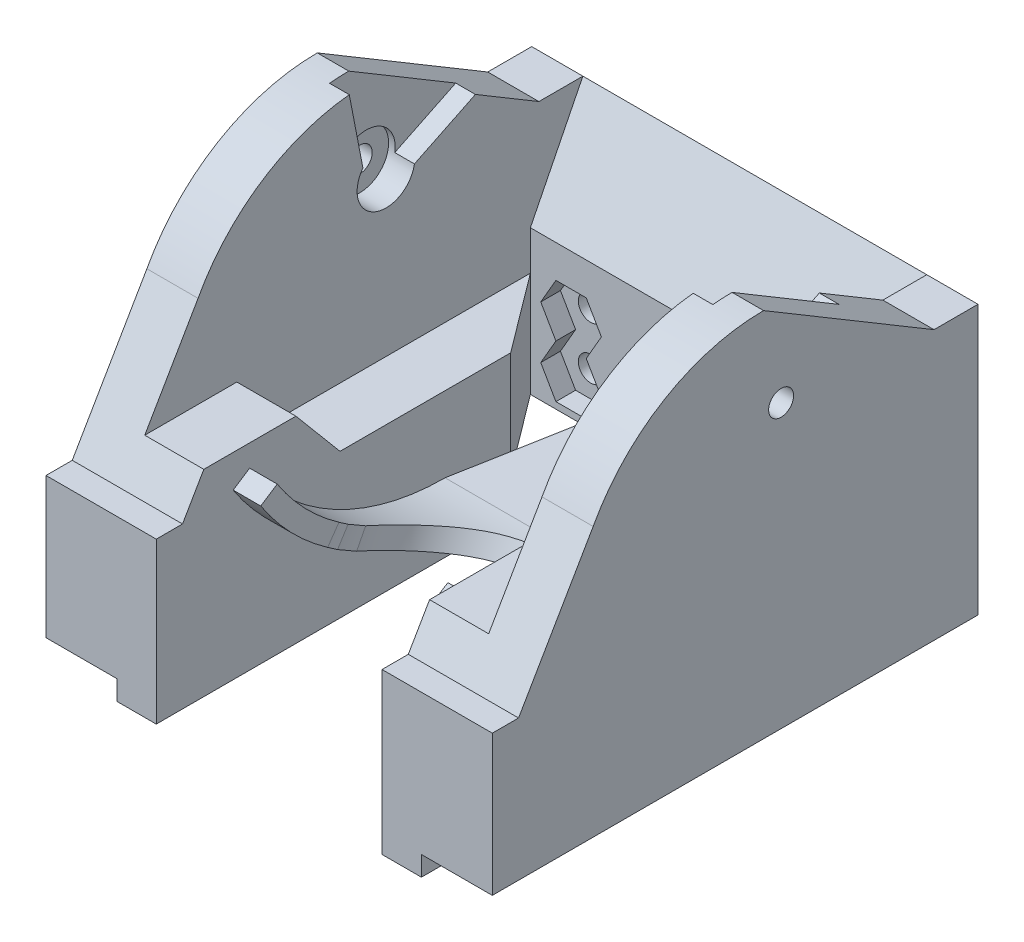
SolidWorks part; units mm, degrees
ref_plane "Alzado" through (0, 0, 0) normal (0, 0, 1) x (1, 0, 0)
ref_plane "Planta" through (0, 0, 0) normal (0, 1, 0) x (1, 0, 0)
ref_plane "Vista lateral" through (0, 0, 0) normal (1, 0, 0) x (0, 0, -1)
sketch "Croquis1" plane through (0, 0, 0) normal (0, 0, 1) x (1, 0, 0)
  line L1 (-48.8873, 14.6225) -> (-14.8873, 14.6225)
  line L2 (-48.8873, 14.6225) -> (-48.8873, -4.3775)
  line L3 (-48.8873, -4.3775) -> (-14.8873, -4.3775)
  line L4 (-14.8873, 14.6225) -> (-14.8873, -4.3775)
  dimension "D1" = 19
  dimension "D2" = 34
extrude "Saliente-Extruir1" add sketch "Croquis1" along normal blind 35
sketch "Croquis2" plane through (0, -4.3775, 0) normal (0, -1, 0) x (1, 0, 0)
  line L0 (-48.8873, 35) -> (-14.8873, 35) construction
  line L1 (-44.9873, 35) -> (-18.7873, 35)
  line L2 (-44.9873, 35) -> (-44.9873, 4)
  line L3 (-44.9873, 4) -> (-18.7873, 4)
  line L4 (-18.7873, 35) -> (-18.7873, 4)
  line L5 (-48.8873, 35) -> (-48.8873, 0) construction
  line L6 (-14.8873, 35) -> (-14.8873, 0) construction
  line L7 (-48.8873, 0) -> (-14.8873, 0) construction
  dimension "D1" = 3.9
  dimension "D2" = 3.9
  dimension "D3" = 26.2
  dimension "D4" = 4
extrude "Cortar-Extruir1" cut sketch "Croquis2" against normal blind 25
sketch "Croquis4" plane through (-18.7873, 0, 0) normal (-1, 0, 0) x (0, 0, 1)
  line L0 (4, 14.6225) -> (4, 6.6225)
  line L1 (4, 14.6225) -> (4, -4.3775) construction
  line L2 (4, 6.6225) -> (0, 14.6225)
  line L3 (0, 14.6225) -> (4, 14.6225)
extrude "Cortar-Extruir3" cut sketch "Croquis4" along normal up to vertex (26.2 mm away) up to point (-44.9873, 14.6225, 4)
sketch "Croquis9" plane through (-14.8873, 0, 0) normal (1, 0, 0) x (0, 0, -1)
  line L0 (-35, 14.6225) -> (0, 14.6225) construction
  line L1 (-29.3158, 14.6225) -> (-3.3495, 14.6225)
  line L7 (-35, -4.3775) -> (0, -4.3775) construction
  arc A0 (-29.3158, 14.6225) -> (-3.3495, 14.6225) centre (-16.3327, 7.6225) cw
  dimension "D2" = 12
extrude "Saliente-Extruir2" add sketch "Croquis9" against normal up to vertex (34 mm away) up to point (-48.8873, 14.6225, 35)
sketch "Croquis10" plane through (0, 14.6225, 0) normal (0, -1, 0) x (1, 0, 0)
  line L1 (-44.9873, 29.3158) -> (-18.7873, 29.3158)
  line L2 (-44.9873, 29.3158) -> (-44.9873, 3.3495)
  line L3 (-44.9873, 3.3495) -> (-18.7873, 3.3495)
  line L4 (-18.7873, 29.3158) -> (-18.7873, 3.3495)
extrude "Cortar-Extruir4" cut sketch "Croquis10" against normal blind 10
sketch "Croquis18" plane through (0, 0, 0) normal (0, 0, -1) x (-1, 0, 0)
  line L0 (48.8873, -4.3775) -> (14.8873, -4.3775) construction
  line L2 (48.8873, 14.6225) -> (48.8873, -4.3775) construction
  circle A0 centre (41.8873, -1.8775) radius 0.95
  circle A1 centre (21.8873, -1.8775) radius 0.95
  circle A2 centre (21.8873, 2.1225) radius 0.95
  circle A3 centre (41.8873, 2.1225) radius 0.95
  dimension "D1" = 2.5
  dimension "D2" = 7
  dimension "D5" = 4
  dimension "D3" = 2
  dimension "D4" = 2
extrude "Cortar-Extruir11" cut sketch "Croquis18" against normal up to vertex (4 mm away) up to point (-18.7873, -4.3775, 4)
sketch "Croquis19" plane through (0, 0, 4) normal (0, 0, 1) x (1, 0, 0)
  line L0 (-44.1973, -1.8775) -> (-43.0423, -3.878)
  line L1 (-24.1973, -1.8775) -> (-23.0423, -3.878)
  line L2 (-23.0423, -3.878) -> (-20.7323, -3.878)
  line L3 (-20.7323, -3.878) -> (-19.5773, -1.8775)
  line L4 (-19.5773, -1.8775) -> (-20.732, 0.1225)
  line L6 (-23.0426, 0.1225) -> (-24.1973, -1.8775)
  line L7 (-43.0423, -3.878) -> (-40.7323, -3.878)
  line L8 (-40.7323, -3.878) -> (-39.5773, -1.8775)
  line L9 (-39.5773, -1.8775) -> (-40.732, 0.1225)
  line L11 (-43.0426, 0.1225) -> (-44.1973, -1.8775)
  line L12 (-44.1973, 2.1225) -> (-43.0426, 0.1225)
  line L14 (-40.732, 0.1225) -> (-39.5773, 2.1225)
  line L15 (-39.5773, 2.1225) -> (-40.7323, 4.1231)
  line L16 (-40.7323, 4.1231) -> (-43.0423, 4.1231)
  line L17 (-43.0423, 4.1231) -> (-44.1973, 2.1225)
  line L18 (-24.1973, 2.1225) -> (-23.0426, 0.1225)
  line L20 (-20.732, 0.1225) -> (-19.5773, 2.1225)
  line L21 (-19.5773, 2.1225) -> (-20.7323, 4.1231)
  line L22 (-20.7323, 4.1231) -> (-23.0423, 4.1231)
  line L23 (-23.0423, 4.1231) -> (-24.1973, 2.1225)
  line L45 (-20.7323, 0.1231) -> (-23.0423, 0.1231) [skipped]
  line L46 (-23.0423, 0.122) -> (-20.7323, 0.122) [skipped]
  line L47 (-43.0423, 0.122) -> (-40.7323, 0.122) [skipped]
  circle A0 centre (-41.8873, -1.8775) radius 2.0005 construction
  circle A1 centre (-21.8873, -1.8775) radius 2.0005 construction
  circle A2 centre (-41.8873, 2.1225) radius 2.0005 construction
  circle A3 centre (-21.8873, 2.1225) radius 2.0005 construction
  dimension "D2" = 2
  dimension "D3" = 2
extrude "Cortar-Extruir12" cut sketch "Croquis19" against normal blind 1.5
sketch "Croquis21" plane through (-14.8873, 0, 0) normal (1, 0, 0) x (0, 0, -1)
  line L0 (0, -4.3775) -> (0, 14.6225) construction
  line L2 (-35, -4.3775) -> (0, -4.3775) construction
  circle A0 centre (-15, 15.6225) radius 0.95
  dimension "D1" = 15
  dimension "D2" = 20
extrude "Cortar-Extruir14" cut sketch "Croquis21" against normal up to vertex (34 mm away) up to point (-48.8873, 14.6225, 3.3495)
sketch "Croquis23" plane through (0, -4.3775, 0) normal (0, -1, 0) x (1, 0, 0)
  line L0 (-44.9873, 35) -> (-40.4873, 35)
  line L1 (-40.4873, 35) -> (-40.4873, 10)
  line L2 (-40.4873, 10) -> (-44.9873, 4)
  line L3 (-44.9873, 35) -> (-44.9873, 4) construction
  line L4 (-44.9873, 4) -> (-44.9873, 35)
  line L5 (-18.7873, 35) -> (-23.2873, 35)
  line L6 (-23.2873, 35) -> (-23.2873, 10)
  line L7 (-23.2873, 10) -> (-18.7873, 4)
  line L8 (-18.7873, 4) -> (-18.7873, 35)
  dimension "D1" = 25
  dimension "D2" = 25
extrude "Saliente-Extruir3" add sketch "Croquis23" against normal blind 8
sketch "Croquis25" plane through (0, -4.3775, 0) normal (0, -1, 0) x (1, 0, 0)
  line L0 (-40.4873, 35) -> (-43.4873, 35)
  line L1 (-20.2873, 35) -> (-23.2873, 35)
  line L2 (-43.4873, 35) -> (-43.4873, 10)
  line L3 (-43.4873, 10) -> (-40.4873, 10)
  line L4 (-40.4873, 35) -> (-40.4873, 10)
  line L10 (-20.2873, 35) -> (-20.2873, 10)
  line L11 (-20.2873, 10) -> (-23.2873, 10)
  line L12 (-23.2873, 35) -> (-23.2873, 10)
  dimension "D1" = 3
  dimension "D2" = 3
extrude "Saliente-Extruir4" add sketch "Croquis25" along normal blind 3
sketch "Croquis43" plane through (0, 3.6225, 0) normal (0, 1, 0) x (1, 0, 0)
  line L0 (-23.2873, -35) -> (-23.2873, -10) construction
  line L1 (-18.7873, -35) -> (-23.2873, -35)
  line L2 (-18.7873, -35) -> (-18.7873, -23)
  line L3 (-18.7873, -23) -> (-23.2873, -23)
  line L4 (-23.2873, -35) -> (-23.2873, -23)
  line L5 (-44.9873, -35) -> (-44.9873, -4) construction
  line L6 (-40.4873, -35) -> (-44.9873, -35)
  line L7 (-40.4873, -35) -> (-40.4873, -23)
  line L8 (-40.4873, -23) -> (-44.9873, -23)
  line L9 (-44.9873, -35) -> (-44.9873, -23)
  dimension "D1" = 12
  dimension "D2" = 12
extrude "Saliente-Extruir8" add sketch "Croquis43" along normal blind 4
sketch "Croquis27" plane through (-14.8873, 0, 0) normal (1, 0, 0) x (0, 0, -1)
  line L0 (-13.5494, -0.9426) -> (-12.6355, -5.8873)
  line L1 (-33.492, 4.3837) -> (-29.3712, 7.2574)
  arc A2 (-29.3712, 7.2574) -> (-13.5494, -0.9426) centre (-15, 15.6225) ccw
  arc A3 (-33.492, 4.3837) -> (-12.6355, -5.8873) centre (-15, 15.6225) ccw
  dimension "D2" = 21.6395
sketch "Croquis29" plane through (-18.7873, 0, 0) normal (-1, 0, 0) x (0, 0, 1)
  line L0 (17.7974, 22.2996) -> (16.5, 15.6225)
  line L1 (6.2969, 18.4321) -> (13.7431, 14.804)
  arc A0 (6.2969, 18.4321) -> (17.7974, 22.2996) centre (16.3327, 7.6225) cw
  arc A1 (29.3158, 14.6225) -> (3.3495, 14.6225) centre (16.3327, 7.6225) ccw construction
  arc A2 (16.5, 15.6225) -> (13.7431, 14.804) centre (15, 15.6225) cw
extrude "Cortar-Extruir20" cut sketch "Croquis29" against normal blind 1.5
extrude "Cortar-Extruir21" cut sketch "Croquis29<2>" along normal blind 27.7
sketch "Croquis29<2>" plane through (-18.7873, 0, 0) normal (-1, 0, 0) x (0, 0, 1) same geometry as "Croquis29"
sketch "Croquis30" plane through (-48.8873, 0, 0) normal (-1, 0, 0) x (0, 0, 1)
  line L0 (29.3158, 14.6225) -> (35, 4.8278)
  line L1 (35, 14.6225) -> (35, -4.3775) construction
  line L2 (35, 4.8278) -> (35, 14.6225)
  line L3 (35, 14.6225) -> (29.3158, 14.6225)
extrude "Cortar-Extruir22" cut sketch "Croquis30" against normal up to vertex (34 mm away) up to point (-14.8873, 14.6225, 35)
sketch "Croquis35" plane through (0, -4.3775, 0) normal (0, -1, 0) x (1, 0, 0)
  line L0 (-20.2873, 23.2623) -> (-14.8873, 23.2623)
  line L2 (-20.2873, 23.2623) -> (-14.8873, 23.2623) construction
  line L4 (-14.8873, 23.2623) -> (-14.8873, 27.7963)
  line L5 (-14.8873, 35) -> (-14.8873, 0) construction
  line L6 (-14.8873, 27.7963) -> (-20.2873, 23.2623)
sketch "Croquis36" plane through (-18.7873, 0, 0) normal (-1, 0, 0) x (0, 0, 1)
  circle A0 centre (15, 15.6225) radius 2.2
extrude "Cortar-Extruir24" cut sketch "Croquis36" against normal blind 2
extrude "Cortar-Extruir25" cut sketch "Croquis36<2>" along normal blind 28.2
sketch "Croquis36<2>" plane through (-18.7873, 0, 0) normal (-1, 0, 0) x (0, 0, 1) same geometry as "Croquis36"
sketch "Croquis38" plane through (-48.8873, 0, 0) normal (-1, 0, 0) x (0, 0, 1)
  line L0 (3.3495, 14.6225) -> (16.3327, 22.3725)
  line L1 (16.3327, 22.3725) -> (3.3495, 22.3725)
  line L2 (3.3495, 22.3725) -> (3.3495, 14.6225)
  arc A0 (29.3158, 14.6225) -> (3.3495, 14.6225) centre (16.3327, 7.6225) ccw construction
extrude "Cortar-Extruir26" cut sketch "Croquis38" against normal up to vertex (34 mm away) up to point (-14.8873, 14.6225, 3.3495)
sketch "Croquis40" plane through (-48.8873, 0, 0) normal (-1, 0, 0) x (0, 0, 1)
  line L0 (24.4625, 4.9679) -> (27.805, 0.9845)
  line L1 (27.805, 0.9845) -> (27.1921, 0.4702)
  line L2 (27.1921, 0.4702) -> (23.8496, 4.4537)
  line L3 (23.5, 4.1807) -> (26.4826, -0.0789)
  line L4 (26.4826, -0.0789) -> (25.8272, -0.5377)
  line L5 (25.8272, -0.5377) -> (22.8446, 3.7219)
  line L6 (22.4696, 3.4848) -> (25.0696, -1.0186)
  line L7 (24.4625, 4.9679) -> (23.8496, 4.4537)
  line L8 (25.0696, -1.0186) -> (24.3768, -1.4186)
  line L9 (24.3768, -1.4186) -> (21.7768, 3.0848)
  line L10 (22.8446, 3.7219) -> (23.5, 4.1807)
  line L11 (21.3819, 2.8831) -> (23.5795, -1.8297)
  line L12 (23.5795, -1.8297) -> (22.8544, -2.1678)
  line L13 (22.4696, 3.4848) -> (21.7768, 3.0848)
  line L14 (22.8544, -2.1678) -> (20.6568, 2.545)
  line L16 (21.3819, 2.8831) -> (20.6568, 2.545)
  circle A1 centre (15, 15.6225) radius 0.95 construction
  dimension "D2" = 14.2443
  dimension "D3" = 14.248
  dimension "D4" = 14.2464
  dimension "D5" = 0.8
  dimension "D6" = 14.2429
  dimension "D8" = 0.8
  dimension "D9" = 0.8
  dimension "D11" = 0.8
sketch "Croquis41" plane through (-20.2873, 0, 0) normal (1, 0, 0) x (0, 0, -1)
  line L0 (-10, -4.3775) -> (-10, -7.3775)
  line L1 (-10, -7.3775) -> (-10, -4.3775) construction
  line L2 (-10, -7.3775) -> (-13, -7.3775)
  line L3 (-10, -7.3775) -> (-35, -7.3775) construction
  line L4 (-13, -7.3775) -> (-10, -4.3775)
extrude "Cortar-Extruir28" cut sketch "Croquis41" against normal up to vertex (23.2 mm away) up to point (-43.4873, -7.3775, 10)
sketch "Croquis44" plane through (-18.7873, 0, 0) normal (-1, 0, 0) x (0, 0, 1)
  line L0 (23, 7.6225) -> (26.3626, 7.6225)
  line L1 (33.3781, 7.6225) -> (23, 7.6225) construction
  line L2 (26.3626, 7.6225) -> (23, 3.6225)
  line L3 (23, 3.6225) -> (23, 7.6225)
extrude "Cortar-Extruir29" cut sketch "Croquis44" along normal up to vertex (26.2 mm away) up to point (-44.9873, 7.6225, 23)
sketch "Croquis24" plane through (-14.8873, 0, 0) normal (1, 0, 0) x (0, 0, -1)
  line L0 (-15, -3.6275) -> (-15, -5.1273)
  line L1 (-31.1427, 5.1356) -> (-32.3723, 4.2754)
  arc A2 (-31.1427, 5.1356) -> (-15, -3.6275) centre (-15, 15.6225) ccw
  arc A3 (-32.3723, 4.2754) -> (-15, -5.1273) centre (-15, 15.6225) ccw
  dimension "D1" = 19.25
  dimension "D2" = 20.7498
sketch "Croquis45" plane through (-23.2873, 0, 0) normal (-1, 0, 0) x (0, 0, 1)
  line L2 (15, -3.6275) -> (15, -5.1273) construction
  line L3 (15, 15.6225) -> (31.1427, 5.1356) construction
  line L4 (15, -3.6275) -> (15, 15.6225) construction
  line L5 (31.1427, 5.1356) -> (29.8848, 5.9527)
  line L6 (15, -3.6275) -> (15, -2.1275)
  arc A0 (15, -3.6275) -> (31.1427, 5.1356) centre (15, 15.6225) ccw construction
  arc A2 (15, -3.6275) -> (31.1427, 5.1356) centre (15, 15.6225) ccw
  arc A3 (29.8848, 5.9527) -> (15, -2.1275) centre (15, 15.6225) cw
extrude "Saliente-Extruir9" add sketch "Croquis45" along normal up to vertex (17.2 mm away) separate body up to point (-40.4873, -7.3775, 13)
ref_plane "Plano1" through (-31.8873, 4.2754, 32.3723) normal (1, 0, 0) x (0, 0, -1)
sketch "Croquis47" plane through (-31.8873, 4.2754, 32.3723) normal (1, 0, 0) x (0, 0, -1)
  line L0 (17.3723, 11.3471) -> (17.3723, -21.3789) construction
  line L1 (17.3723, 11.3471) -> (0.4676, -24.9052) construction
  line L2 (17.3723, 11.3471) -> (-2.6277, -23.2939) construction
  line L3 (17.3723, 11.3471) -> (-5.5707, -21.419) construction
  line L4 (17.3723, 11.3471) -> (-5.5707, -21.419)
  line L5 (17.3723, 11.3471) -> (-2.6277, -23.2939)
  line L6 (17.3723, 11.3471) -> (0.4676, -24.9052)
  dimension "D1" = 25
  dimension "D2" = 30
  dimension "D3" = 35
ref_plane "Plano2" through (-31.8873, -17.1435, 37.9431) normal (0, -0.8192, 0.5736) x (-1, 0, 0)
sketch "Croquis48" plane through (-31.8873, -17.1435, 37.9431) normal (0, -0.8192, 0.5736) x (-1, 0, 0)
  line L3 (6.5, 0) -> (6.5, -15)
  line L4 (6.5, -15) -> (-6.5, -15)
  line L5 (-6.5, -15) -> (-6.5, 0)
  arc A2 (6.5, 0) -> (-6.5, 0) centre (0, 0) ccw
ref_plane "Plano3" through (-31.8873, -19.0185, 35) normal (0, -0.866, 0.5) x (-1, 0, 0)
ref_plane "Plano4" through (-31.8873, -20.6298, 31.9047) normal (0, -0.9063, 0.4226) x (-1, 0, 0)
sketch "Croquis49" plane through (-31.8873, -19.0185, 35) normal (0, -0.866, 0.5) x (-1, 0, 0)
  circle A0 centre (0, 0) radius 6.5
sketch "Croquis50" plane through (-31.8873, -20.6298, 31.9047) normal (0, -0.9063, 0.4226) x (-1, 0, 0)
  circle A0 centre (0, 0) radius 6.5
sweep "Cortar-Barrer2" cut profiles "Croquis48" path "Croquis47"
sketch "Croquis51" plane through (-31.8873, 4.2754, 32.3723) normal (1, 0, 0) x (0, 0, -1)
  line L0 (17.3723, 11.3471) -> (-2.6277, -23.2939)
sweep "Cortar-Barrer3" cut profiles "Croquis49" path "Croquis51"
sketch "Croquis52" plane through (-31.8873, 4.2754, 32.3723) normal (1, 0, 0) x (0, 0, -1)
  line L0 (17.3723, 11.3471) -> (0.4676, -24.9052)
sweep "Cortar-Barrer4" cut profiles "Croquis50" path "Croquis52"
sketch "Croquis56" plane through (0, 0, 35) normal (0, 0, 1) x (1, 0, 0)
  line L0 (-23.2873, -7.3775) -> (-20.2873, -7.3775)
  line L1 (-20.2873, -7.3775) -> (-20.2873, -4.3775)
  line L2 (-20.2873, -4.3775) -> (-14.8873, -4.3775)
  line L3 (-14.8873, -4.3775) -> (-14.8873, 4.8278)
  line L4 (-14.8873, 4.8278) -> (-23.2873, 4.8278)
  line L5 (-23.2873, 4.8278) -> (-23.2873, -7.3775)
  line L6 (-40.4873, -7.3775) -> (-40.4873, 4.8278)
  line L7 (-40.4873, 4.8278) -> (-48.8873, 4.8278)
  line L8 (-48.8873, 4.8278) -> (-48.8873, -4.3775)
  line L9 (-48.8873, -4.3775) -> (-43.4873, -4.3775)
  line L10 (-43.4873, -4.3775) -> (-43.4873, -7.3775)
  line L11 (-43.4873, -7.3775) -> (-40.4873, -7.3775)
extrude "Saliente-Extruir15" add sketch "Croquis56" along normal blind 2
sketch "Croquis58" plane through (0, 0, 37) normal (0, 0, 1) x (1, 0, 0)
  line L0 (-40.4873, -7.3775) -> (-40.4873, 4.8278) construction
  line L2 (-40.4873, -1.2748) -> (-40.4873, 6.807)
  line L3 (-40.4873, 6.807) -> (-23.2873, 6.807)
  line L4 (-23.2873, -1.2748) -> (-23.2873, 6.807)
  line L5 (-23.2873, -1.2748) -> (-23.2873, -3.2748)
  line L6 (-23.2873, 4.8278) -> (-23.2873, -7.3775) construction
  line L7 (-23.2873, -3.2748) -> (-40.4873, -3.2748)
  line L8 (-40.4873, -3.2748) -> (-40.4873, -1.2748)
ref_plane "Plano5" through (0, -3.6275, 0) normal (0, -1, 0) x (1, 0, 0)
sketch "Croquis59" plane through (0, -3.6275, 0) normal (0, -1, 0) x (1, 0, 0)
  line L0 (-40.4873, 15) -> (-23.2873, 15)
  line L4 (-40.4873, 3.9998) -> (-38.4873, 3.9998) construction
  line L5 (-23.2873, 3.9998) -> (-25.2873, 3.9998) construction
  line L6 (-25.2873, 3.9998) -> (-23.2873, 15)
  line L7 (-40.4873, 15) -> (-38.4873, 3.9998)
  line L8 (-38.4873, 3.9998) -> (-25.2873, 3.9998)
extrude "Saliente-Extruir29" add sketch "Croquis59" against normal blind 1.5 separate body
sketch "Croquis60" plane through (0, -4.3775, 0) normal (0, -1, 0) x (1, 0, 0)
  line L1 (-48.8873, 35) -> (-48.8873, 0)
  line L2 (-43.4873, 35) -> (-43.4873, 10)
  line L3 (-43.4873, 10) -> (-48.8873, 0)
  line L4 (-14.8873, 0) -> (-14.8873, 37)
  line L5 (-14.8873, 37) -> (-20.2873, 37)
  line L6 (-20.2873, 37) -> (-20.2873, 10)
  line L7 (-20.2873, 10) -> (-14.8873, 0)
  line L9 (-48.8873, 35) -> (-48.8873, 37)
  line L10 (-48.8873, 37) -> (-43.4873, 37)
  line L11 (-43.4873, 37) -> (-43.4873, 35)
extrude "Saliente-Extruir30" add sketch "Croquis60" along normal blind 1.5
